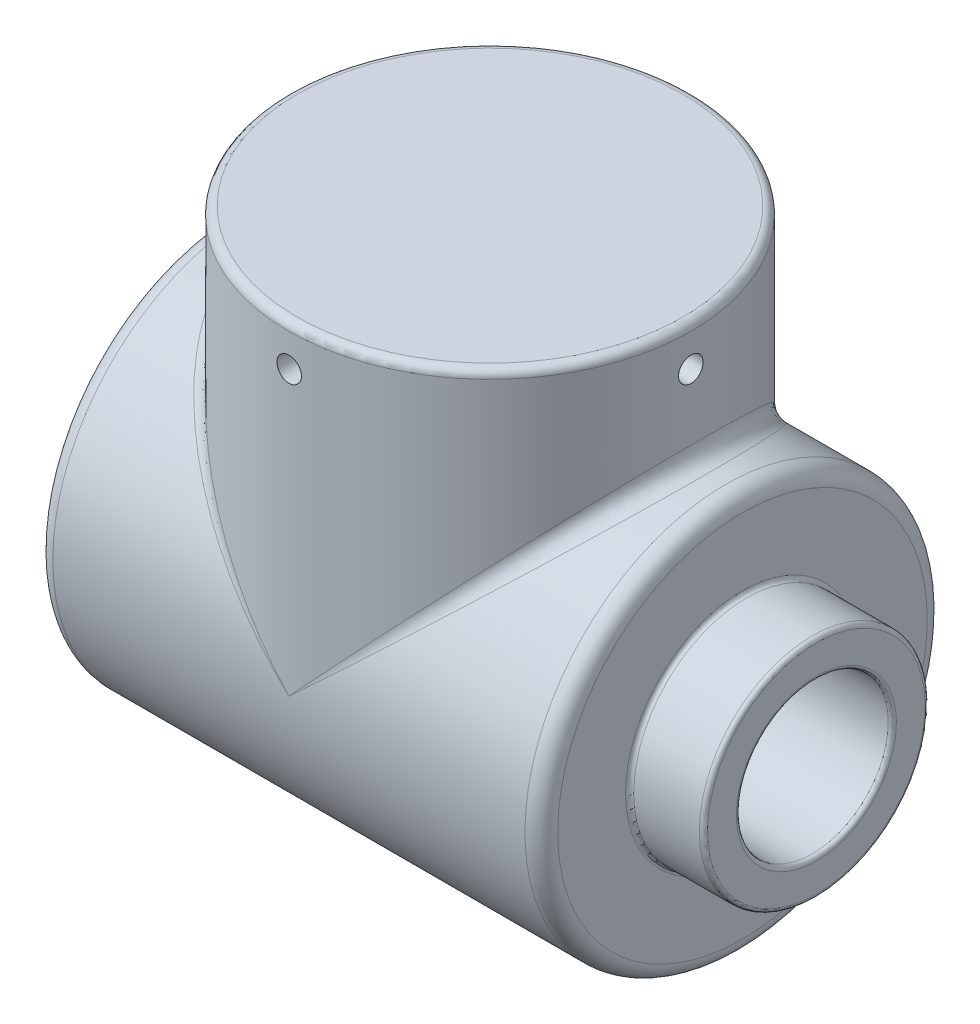
SolidWorks part; units mm, degrees
ref_plane "Front Plane" through (0, 0, 0) normal (0, 0, 1) x (1, 0, 0)
ref_plane "Top Plane" through (0, 0, 0) normal (0, 1, 0) x (1, 0, 0)
ref_plane "Right Plane" through (0, 0, 0) normal (1, 0, 0) x (0, 0, -1)
sketch "Sketch2" plane through (0, 0, 0) normal (0, 0, 1) x (1, 0, 0)
  line L1 (89.65, 0) -> (-89.65, 0)
  line L2 (89.65, 0) -> (89.65, 49)
  line L3 (89.65, 49) -> (-89.65, 49)
  line L4 (-89.65, 0) -> (-89.65, 49)
  point P4 (0, 0)
  dimension "D1" = 179.3
  dimension "D2" = 49
revolve "Revolve1" [suppressed] add sketch "Sketch2" angle 360 about L1
sketch "Sketch3" [suppressed] plane through (89.65, 0, 0) normal (1, 0, 0) x (0, 0, -1)
  circle A0 centre (0, 0) radius 15
  dimension "D1" = 30
extrude "Cut-Extrude1" [suppressed] cut sketch "Sketch3" against normal blind 210
sketch "Sketch4" plane through (0, 0, 0) normal (0, 0, 1) x (1, 0, 0)
  line L0 (-61.5, 0) -> (79.5, 0)
  line L1 (79.5, 0) -> (79.5, 27.5)
  line L2 (79.5, 27.5) -> (61.5, 27.5)
  line L3 (61.5, 27.5) -> (61.5, 49)
  line L4 (61.5, 49) -> (-61.5, 49)
  line L5 (-61.5, 49) -> (-61.5, 0)
  line L6 (0, 49) -> (0, 0) construction
  dimension "D1" = 123
  dimension "D2" = 18
  dimension "D3" = 27.5
  dimension "D4" = 49
revolve "Revolve2" add sketch "Sketch4" angle 360 about L0
sketch "Sketch5" plane through (79.5, 0, 0) normal (1, 0, 0) x (0, 0, -1)
  circle A0 centre (0, 0) radius 18.5
  dimension "D1" = 37
extrude "Cut-Extrude2" cut sketch "Sketch5" against normal blind 138
ref_plane "Plane1" through (0, 49, 0) normal (0, 1, 0) x (1, 0, 0)
sketch "Sketch6" plane through (0, 49, 0) normal (0, 1, 0) x (1, 0, 0)
  line L1 (-63.125, 34.425) -> (31.125, 34.425)
  line L2 (-63.125, 34.425) -> (-63.125, -34.425)
  line L3 (-63.125, -34.425) -> (31.125, -34.425)
  line L4 (31.125, 34.425) -> (31.125, -34.425)
  line L6 (-61.5, 0) -> (61.5, 0) construction
  line L7 (-61.5, 49) -> (-61.5, -49) construction
  line L8 (61.5, -49) -> (61.5, 49) construction
  line L9 (-16, 63.5465) -> (-16, -66.4968) construction
  point P4 (-16, -34.425)
  point P5 (-63.125, 0)
  dimension "D1" = 77.5
  dimension "D2" = 94.25
  dimension "D3" = 68.85
extrude "Boss-Extrude1" [suppressed] add sketch "Sketch6" along normal blind 30 and the other way up to surface other way up to face at (-61.5, -49, 0)
fillet "Fillet2" [suppressed] radius 30
ref_plane "Plane2" [suppressed] through (14.625, 0, 0) normal (1, 0, 0) x (0, 0, -1)
ref_plane "Plane3" [suppressed] through (-59.625, 0, 0) normal (-1, 0, 0) x (0, 0, 1)
sketch "Sketch7" [suppressed] plane through (14.625, 0, 0) normal (1, 0, 0) x (0, 0, -1)
  line L1 (-40, 196) -> (40, 196)
  line L2 (-40, 196) -> (-40, 166)
  line L3 (-40, 166) -> (40, 166)
  line L4 (40, 196) -> (40, 166)
  line L5 (0, 34.5583) -> (0, 302.6635) construction
  point P9 (0, 196)
  dimension "D1" = 80
  dimension "D2" = 30
  dimension "D3" = 166
ref_plane "Plane4" [suppressed] through (36.625, 0, 0) normal (1, 0, 0) x (0, 0, -1)
ref_plane "Plane5" through (0, 250, 0) normal (0, 1, 0) x (1, 0, 0)
sketch "Sketch8" [suppressed] plane through (0, 250, 0) normal (0, 1, 0) x (1, 0, 0)
  line L0 (36.625, -85.597) -> (36.625, 85.597) construction
  line L1 (36.625, 40) -> (66.625, 40)
  line L2 (36.625, 40) -> (36.625, -40)
  line L3 (36.625, -40) -> (66.625, -40)
  line L4 (66.625, 40) -> (66.625, -40)
  line L5 (-101.8526, 0) -> (154.8726, 0) construction
  point P9 (36.625, 0)
  dimension "D1" = 30
  dimension "D2" = 80
loft "Loft1" [suppressed] add profiles "Sketch7", "Sketch8" start constraint normal to profile start tangent length 1.4
sketch "Sketch9" [suppressed] plane through (36.625, 0, 0) normal (1, 0, 0) x (0, 0, -1)
  line L1 (-40, 196.0467) -> (40, 196.0467)
  line L2 (-40, 196.0467) -> (-40, 166)
  line L3 (-40, 166) -> (40, 166)
  line L4 (40, 196.0467) -> (40, 166)
extrude "Boss-Extrude2" [suppressed] add sketch "Sketch9" against normal blind 20
sketch "Sketch10" [suppressed] plane through (36.625, 0, 0) normal (1, 0, 0) x (0, 0, -1)
  line L0 (-50, 250) -> (-50, 300)
  line L3 (50, 250) -> (50, 300)
  line L4 (-50, 250) -> (50, 250)
  line L5 (-50, 300) -> (50, 300) construction
  line L6 (0, 0) -> (0, 363.1332) construction
  line L8 (53.9, 250) -> (-53.9, 250) construction
  arc A0 (-50, 300) -> (50, 300) centre (0, 300) cw
  point P3 (0, 250)
  dimension "D2" = 50
  dimension "D1" = 100
ref_plane "Plane6" [suppressed] through (-12.5, 0, 0) normal (1, 0, 0) x (0, 0, -1)
ref_plane "Plane7" [suppressed] through (0, 0, 0) normal (0, 0, 1) x (1, 0, 0)
ref_plane "Plane8" through (0, 49, 0) normal (0, 1, 0) x (1, 0, 0)
sketch "Sketch11" plane through (0, 49, 0) normal (0, 1, 0) x (1, 0, 0)
  line L0 (0, 49) -> (0, -49) construction
  line L1 (61.5, 49) -> (-61.5, 49) construction
  line L2 (-61.5, -49) -> (61.5, -49) construction
  line L3 (-61.5, 0) -> (61.5, 0) construction
  line L4 (-61.5, 49) -> (-61.5, -49) construction
  line L5 (61.5, -49) -> (61.5, 49) construction
  circle A0 centre (0, 0) radius 49
  dimension "D1" = 98
extrude "Boss-Extrude3" add sketch "Sketch11" along normal blind 30 and the other way up to surface other way up to face at (-61.5, -49, 0)
sketch "Sketch12" plane through (-58.5, 0, 0) normal (1, 0, 0) x (0, 0, -1)
  line L0 (0, 19.7074) -> (0, -15.9367) construction
  circle A0 centre (0, 0) radius 14 construction
  circle A1 centre (0, 14) radius 2.3
  dimension "D1" = 28
  dimension "D2" = 4.6
extrude "Cut-Extrude3" cut sketch "Sketch12" against normal up to next
pattern_circular "CirPattern1" count 6 over 360 about axis through (-58.5, 0, 0) along (1, 0, 0) of "Cut-Extrude3"
ref_plane "Plane9" through (0, 0, 49) normal (0, 0, 1) x (1, 0, 0)
sketch "Sketch14" plane through (0, 0, 49) normal (0, 0, 1) x (1, 0, 0)
  line L1 (-49, 69) -> (49, 69) construction
  line L4 (0, 79) -> (0, 49) construction
  line L5 (49, 79) -> (-49, 79) construction
  line L6 (53.9, 49) -> (-53.9, 49) construction
  circle A0 centre (0, 69) radius 2.975
  dimension "D1" = 5.95
  dimension "D2" = 10
extrude "Cut-Extrude4" cut sketch "Sketch14" against normal blind 7.62 contours A0
mirror "Mirror1" about plane through (0, 0, 0) normal (0, 0, 1) of "Cut-Extrude4"
ref_plane "Plane10" through (49, 0, 0) normal (1, 0, 0) x (0, 0, -1)
sketch "Sketch15" plane through (49, 0, 0) normal (1, 0, 0) x (0, 0, -1)
  line L0 (0, 79) -> (0, 49) construction
  line L1 (49, 79) -> (-49, 79) construction
  line L2 (53.9, 49) -> (-53.9, 49) construction
  line L3 (-49, 69) -> (49.108, 69) construction
  line L4 (-49, 42.35) -> (-49, -42.35) construction
  circle A0 centre (0, 69) radius 2.99
  dimension "D2" = 5.98
  dimension "D1" = 10
extrude "Cut-Extrude5" cut sketch "Sketch15" against normal blind 4.7
mirror "Mirror2" about plane through (0, 0, 0) normal (1, 0, 0) of "Cut-Extrude5" second plane through (49, 0, 0) second plane normal (1, 0, 0)
fillet "Fillet3" radius 2 1 edges at (-49, 79, 0)
fillet "Fillet4" radius 4 2 edges at (-49, 49, 0) (49, 49, 0)
fillet "Fillet5" radius 4 1 edges at (61.5, -49, 0)
fillet "Fillet6" radius 4 1 edges at (-61.5, -49, 0)
fillet "Fillet7" radius 1 3 edges at (79.5, 0, -18.5) (79.5, -27.5, 0) (61.5, -27.5, 0)
fillet "Fillet8" radius 0.5 1 edges at (-58.5, 0, -18.5)
